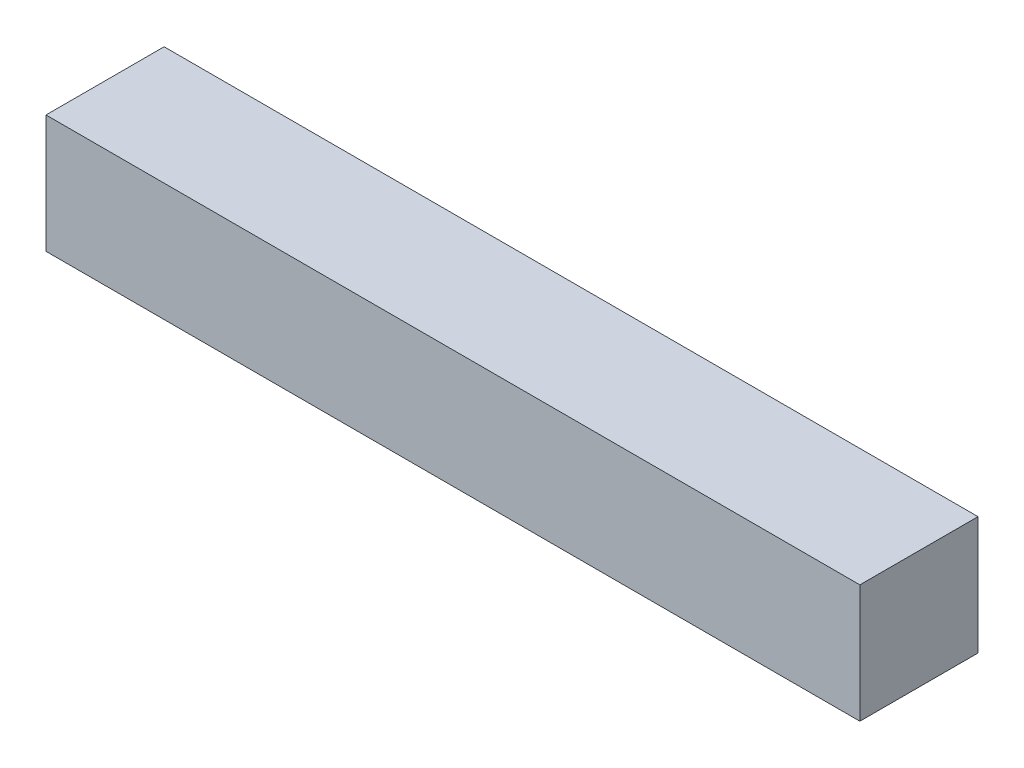
SolidWorks part; units mm, degrees
material "Oak"
ref_plane "Front Plane" through (0, 0, 0) normal (0, 0, 1) x (1, 0, 0)
ref_plane "Top Plane" through (0, 0, 0) normal (0, 1, 0) x (1, 0, 0)
ref_plane "Right Plane" through (0, 0, 0) normal (1, 0, 0) x (0, 0, -1)
sketch "Sketch1" plane through (0, 0, 0) normal (0, 0, 1) x (1, 0, 0)
  line L0 (-175, 25.4) -> (-124.2, -25.4)
  line L1 (-175, 25.4) -> (175, 25.4)
  line L3 (-124.2, -25.4) -> (124.2, -25.4)
  line L5 (0, -25.4) -> (0, 25.4) construction
  line L6 (-149.6, 0) -> (149.6, 0) construction
  line L7 (175, 25.4) -> (124.2, -25.4)
  line L8 (-175, 25.4) -> (-175, -25.4)
  line L9 (-175, -25.4) -> (-124.2, -25.4)
  line L10 (124.2, -25.4) -> (175, -25.4)
  line L11 (175, -25.4) -> (175, 25.4)
  point P0 (0, 0)
  point P10 (-149.6, 0)
  dimension "D1" = 350
  dimension "D2" = 45
  dimension "D3" = 45
  dimension "D4" = 50.8
extrude "Boss-Extrude1" [suppressed] add sketch "Sketch1" along normal mid plane 50.8 contours L7 L1 L0 L3
extrude "Boss-Extrude2" add sketch "Sketch1<3>" along normal blind 50.8 contours L8 L9 L0 | L7 L1 L0 L3 | L10 L11 L7 region at (0, 1.4375, 0) region at (-158.0667, -8.4667, 0) region at (158.0667, -8.4667, 0)
sketch "Sketch1<3>" plane through (0, 0, 0) normal (0, 0, 1) x (1, 0, 0) same geometry as "Sketch1"
